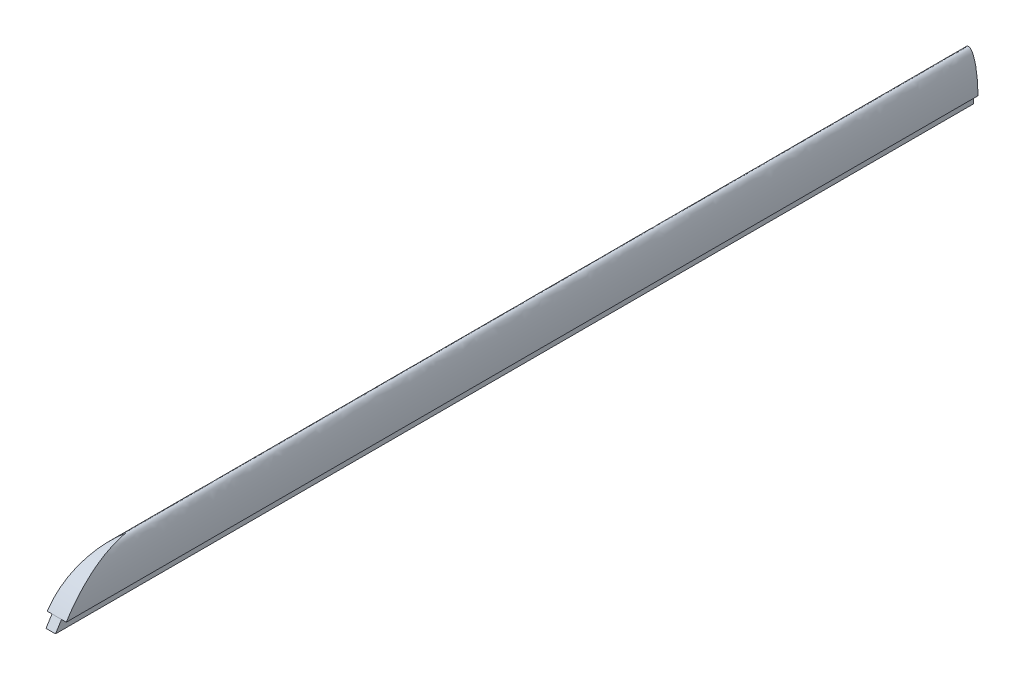
SolidWorks part; units mm, degrees
ref_plane "Front Plane" through (0, 0, 0) normal (0, 0, 1) x (1, 0, 0)
ref_plane "Top Plane" through (0, 0, 0) normal (0, 1, 0) x (1, 0, 0)
ref_plane "Right Plane" through (0, 0, 0) normal (1, 0, 0) x (0, 0, -1)
sketch "Cross Section" plane through (0, 0, 0) normal (0, 0, 1) x (1, 0, 0)
  line L0 (10, 0) -> (20, 0) construction
  line L1 (0, 80) -> (0, 0) construction
  line L2 (10, 0) -> (20, 0)
  line L4 (-10, 0) -> (-10, -20)
  line L5 (-10, -20) -> (10, -20)
  line L6 (10, 0) -> (10, -20)
  line L7 (-10, 0) -> (10, -20) construction
  line L8 (-10, -20) -> (10, 0) construction
  line L10 (-20, 0) -> (-10, 0)
  line L11 (-10, 0) -> (10, 0) construction
  ellipse E0 centre (0, 0) end of major axis (0, -80) minor radius 20 (20, 0) -> (-20, 0) ccw
  point P2 (0, -10)
  dimension "D1" = 40
  dimension "D2" = 80
  dimension "D3" = 10
extrude "Profile Extrude" add sketch "Cross Section" along normal blind 2000
sketch "Flush Support Cut Sketch" plane through (0, 0, 0) normal (1, 0, 0) x (0, 0, -1)
  line L0 (-2000, -126.1238) -> (-1869.2562, 80)
  line L1 (-1869.2562, 80) -> (-2000, 80)
  line L2 (-2000, 80) -> (-2000, -126.1238)
  line L3 (-2000, 80) -> (-2000, 0) construction
  line L4 (0, 80) -> (-2000, 80) construction
  line L5 (-1920, 0) -> (-1989.8893, -110.1839) construction
extrude "Flush Support Cut" cut sketch "Flush Support Cut Sketch" against normal up to surface and the other way up to surface up to face at (0, 40, 1000) other way up to face at (0, 40, 1000)
sketch "Support Corner Cut Sketch" plane through (0, 0, 0) normal (1, 0, 0) x (0, 0, -1)
  line L0 (-1774.5201, 80) -> (-1869.2562, 80)
  line L1 (-1869.2562, 80) -> (-1920, 0)
  line L2 (-1869.2562, 80) -> (-1920, 0) construction
  line L4 (-1920, 0) -> (0, 0) construction
  line L5 (0, 80) -> (-1869.2562, 80) construction
  arc A0 (-1774.5201, 80) -> (-1920, 0) centre (-1774.5201, -92.2775) ccw
extrude "Support Corner Cut" cut sketch "Support Corner Cut Sketch" against normal up to surface and the other way up to surface up to face at (-1.1641, 0.5496, 972.3374) other way up to face at (-1.1641, 0.5496, 972.3374)
